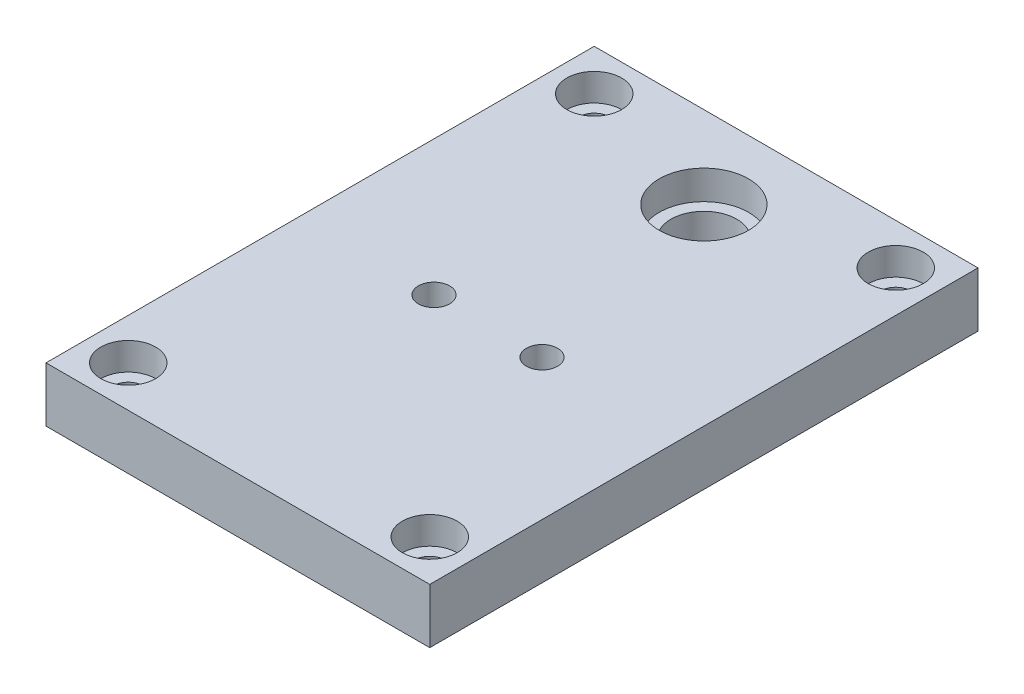
SolidWorks part; units mm, degrees
ref_plane "Front Plane" through (0, 0, 0) normal (0, 0, 1) x (1, 0, 0)
ref_plane "Top Plane" through (0, 0, 0) normal (0, 1, 0) x (1, 0, 0)
ref_plane "Right Plane" through (0, 0, 0) normal (1, 0, 0) x (0, 0, -1)
sketch "Sketch1" plane through (0, 0, 0) normal (0, 1, 0) x (1, 0, 0)
  line L1 (-35, -50) -> (35, -50)
  line L2 (-35, -50) -> (-35, 50)
  line L3 (-35, 50) -> (35, 50)
  line L4 (35, -50) -> (35, 50)
  line L5 (-35, -50) -> (35, 50) construction
  line L6 (-35, 50) -> (35, -50) construction
  point P0 (0, 0)
  dimension "D1" = 70
  dimension "D2" = 100
extrude "Boss-Extrude1" add sketch "Sketch1" along normal blind 10
sketch "Sketch4" plane through (0, 10, 0) normal (0, 1, 0) x (1, 0, 0)
  line L0 (-35, 50) -> (-35, -50) construction
  line L1 (35, 50) -> (-35, 50) construction
  line L3 (35, -50) -> (35, 50) construction
  line L4 (-35, -50) -> (35, -50) construction
  point P0 (-27.5, -42.5)
  point P2 (-27.5, 42.5)
  point P4 (27.5, 42.5)
  point P6 (27.5, -42.5)
  dimension "D1" = 7.5
  dimension "D2" = 7.5
  dimension "D3" = 7.5
  dimension "D4" = 7.5
hole_wizard "CBORE for M5 SHCS1" positions "Sketch4" profile "Sketch3" counterbore size "M5" standard "ANSI Metric" end condition through all
sketch "Sketch3" plane through (-27.5, 10, 42.5) normal (1, 0, 0) x (0, 0, 1)
  line L0 (0, 0) -> (0, 10)
  line L1 (0, 10) -> (2.75, 10)
  line L3 (2.75, 10) -> (2.75, 5)
  line L4 (2.75, 5) -> (5, 5)
  line L5 (5, 5) -> (5, 0)
  line L7 (5, 0) -> (0, 0)
  line L11 (0, -6.35) -> (0, 107.95) construction
  dimension "Thru Hole Dia." = 5.5
  dimension "Thru Hole Depth" = 10
  dimension "C'Bore Dia." = 10
  dimension "C'Bore Depth" = 5
sketch "Sketch7" plane through (0, 10, 0) normal (0, 1, 0) x (1, 0, 0)
  line L0 (35, 50) -> (-35, 50) construction
  point P0 (0, 35)
  point P1 (0, 0)
  dimension "D1" = 15
hole_wizard "Ø1.0mm Dowel Hole1" positions "Sketch7" profile "Sketch6" hole size "Ø1.0" standard "ANSI Metric"
sketch "Sketch6" plane through (0, 10, -35) normal (1, 0, 0) x (0, 0, 1)
  line L0 (0, 0) -> (0, 5.3)
  line L1 (0, 5.3) -> (8.15, 5.3)
  line L2 (8.15, 5.3) -> (8.15, 0)
  line L5 (8.15, 0) -> (0, 0)
  line L10 (0, 5.3) -> (-8.15, 5.3) construction
  line L11 (0, -6.35) -> (0, 107.95) construction
  dimension "Hole Dia." = 16.3
  dimension "Hole Depth" = 5.3
  dimension "Drill Angle" = 180
sketch "Sketch10" plane through (0, 10, 0) normal (0, 1, 0) x (1, 0, 0)
  point P0 (-10.3518, -3.8829)
  point P2 (9.3528, -3.8829)
hole_wizard "Ø1.0mm Dowel Hole2" positions "Sketch10" profile "Sketch9" hole size "Ø1.0" standard "ANSI Metric" end condition through all
sketch "Sketch9" plane through (-10.3518, 10, 3.8829) normal (1, 0, 0) x (0, 0, 1)
  line L0 (0, 0) -> (0, 10)
  line L1 (0, 10) -> (2.85, 10)
  line L2 (2.85, 10) -> (2.85, 0)
  line L5 (2.85, 0) -> (0, 0)
  line L11 (0, -6.35) -> (0, 107.95) construction
  dimension "Thru Hole Dia." = 5.7
  dimension "Thru Hole Depth" = 10
sketch "Sketch13" plane through (0, 4.7, 0) normal (0, 1, 0) x (1, 0, 0)
  point P0 (0, 35)
hole_wizard "Ø1.0mm Dowel Hole3" positions "Sketch13" profile "Sketch12" hole size "Ø1.0" standard "ANSI Metric" end condition through all
sketch "Sketch12" plane through (0, 4.7, -35) normal (1, 0, 0) x (0, 0, 1)
  line L0 (0, 0) -> (0, 4.7)
  line L1 (0, 4.7) -> (6, 4.7)
  line L2 (6, 4.7) -> (6, 0)
  line L5 (6, 0) -> (0, 0)
  line L11 (0, -6.35) -> (0, 107.95) construction
  dimension "Thru Hole Dia." = 12
  dimension "Thru Hole Depth" = 4.7
equation "\"D1@Sketch4\" = 5 * 1.5"
equation "\"D2@Sketch4\" = \"D1@Sketch4\""
